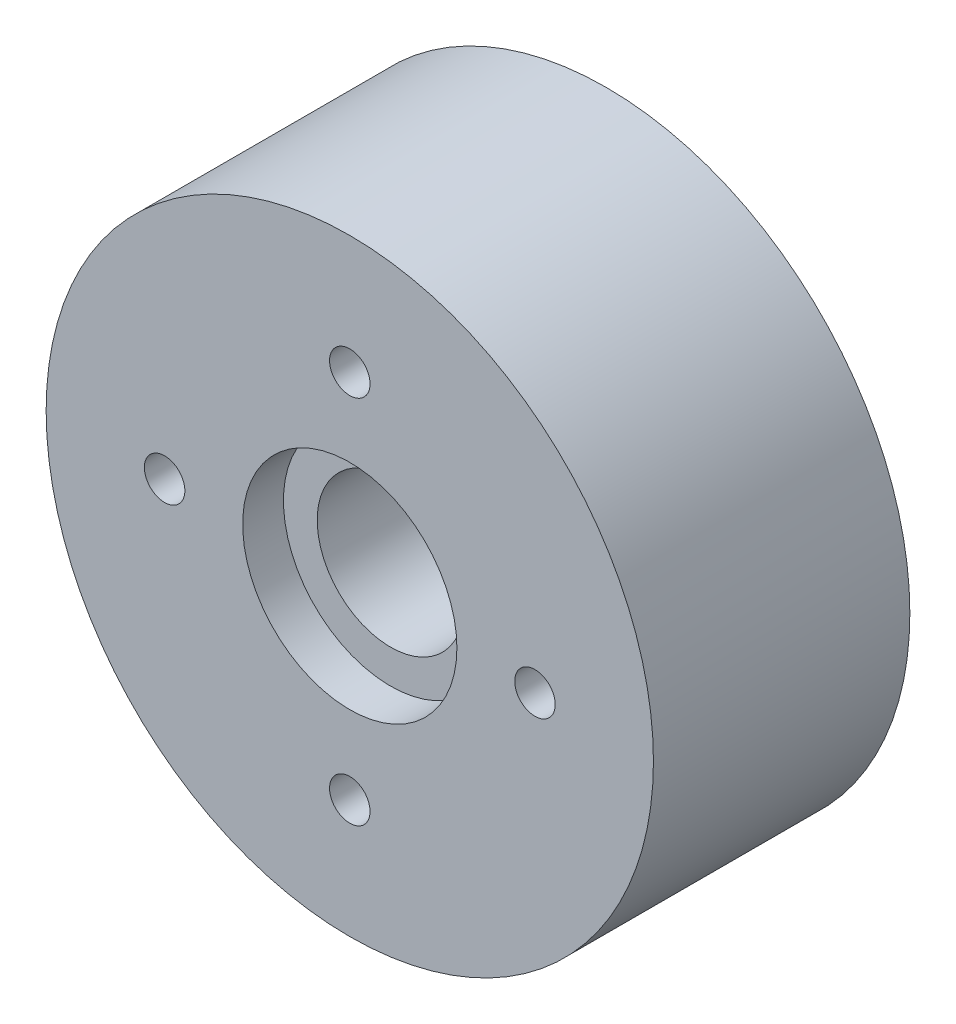
SolidWorks part; units mm, degrees
ref_plane "Front Plane" through (0, 0, 0) normal (0, 0, 1) x (1, 0, 0)
ref_plane "Top Plane" through (0, 0, 0) normal (0, 1, 0) x (1, 0, 0)
ref_plane "Right Plane" through (0, 0, 0) normal (1, 0, 0) x (0, 0, -1)
sketch "Sketch1" plane through (0, 0, 0) normal (0, 0, 1) x (1, 0, 0)
  circle A0 centre (0, 0) radius 22.5
  circle A1 centre (0, 0) radius 7.9375
  dimension "D1" = 45
  dimension "D2" = 15.875
extrude "Boss-Extrude1" add sketch "Sketch1" along normal blind 20
sketch "Sketch2" plane through (0, 0, 20) normal (0, 0, 1) x (1, 0, 0)
  circle A0 centre (0, 13.7209) radius 1.5
  circle A1 centre (13.7209, 0) radius 1.5
  circle A2 centre (0, -13.7209) radius 1.5
  circle A3 centre (-13.7209, 0) radius 1.5
  point P12 (0, 0)
  dimension "D1" = 3
  dimension "D2" = 13.7209
  dimension "D3" = 4
extrude "Cut-Extrude1" cut sketch "Sketch2" against normal through all
sketch "Sketch3" plane through (0, 0, 0) normal (0, 0, 1) x (1, 0, 0)
  circle A0 centre (0, 13.7209) radius 2.75
  circle A1 centre (13.7209, 0) radius 2.75
  circle A2 centre (0, -13.7209) radius 2.75
  circle A3 centre (-13.7209, 0) radius 2.75
  point P12 (0, 0)
  dimension "D1" = 5.5
  dimension "D2" = 4
extrude "Cut-Extrude2" cut sketch "Sketch3" along normal blind 13
ref_plane "Plane1" through (0, 0, 16.9784) normal (0, 0, 1) x (1, 0, 0)
sketch "Sketch4" plane through (0, 0, 16.9784) normal (0, 0, 1) x (1, 0, 0)
  circle A0 centre (0, 0) radius 5.4375
  circle A1 centre (0, 0) radius 7.9375 construction
  circle A2 centre (0, 0) radius 7.9375
  dimension "D1" = 2.5
extrude "Boss-Extrude2" add sketch "Sketch4" against normal through all
sketch "Sketch5" plane through (0, 0, 0) normal (0, 0, -1) x (-1, 0, 0)
  circle A0 centre (0, 0) radius 7.9375 construction
  circle A1 centre (0, 0) radius 5.4375 construction
  circle A2 centre (0, 0) radius 7.9375
  circle A3 centre (0, 0) radius 5.4375
extrude "Cut-Extrude3" cut sketch "Sketch5" against normal blind 3.0216
sketch "Sketch6" plane through (0, 0, 0) normal (0, 0, -1) x (-1, 0, 0)
  circle A0 centre (0, 0) radius 30.0332
extrude "Cut-Extrude4" cut sketch "Sketch6" against normal blind 1
